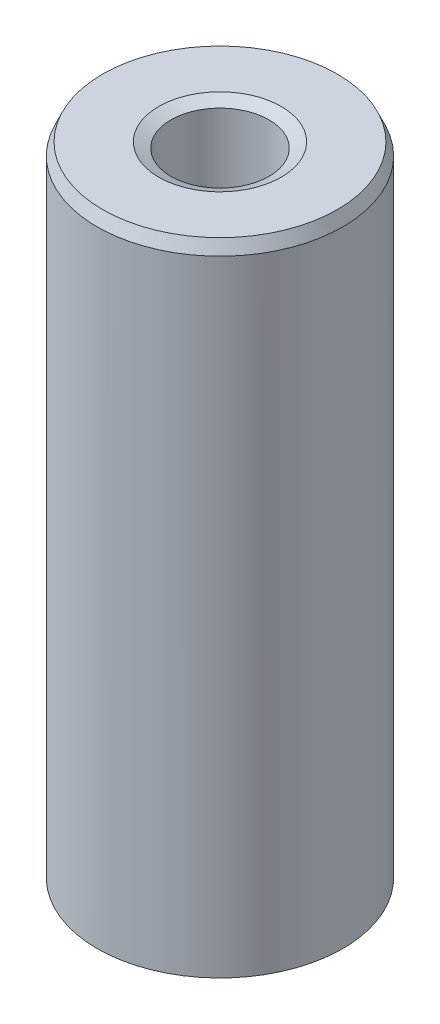
SolidWorks part; units mm, degrees
ref_plane "Front Plane" through (0, 0, 0) normal (0, 0, 1) x (1, 0, 0)
ref_plane "Top Plane" through (0, 0, 0) normal (0, 1, 0) x (1, 0, 0)
ref_plane "Right Plane" through (0, 0, 0) normal (1, 0, 0) x (0, 0, -1)
sketch "Sketch1" plane through (0, 0, 0) normal (0, 1, 0) x (1, 0, 0)
  circle A0 centre (0, 0) radius 7.5
  dimension "SLEEVE_OD" = 15
extrude "Boss-Extrude1" add sketch "Sketch1" along normal blind 39.2579
sketch "Sketch2" plane through (0, 0, 0) normal (0, 1, 0) x (1, 0, 0)
  circle A0 centre (0, 0) radius 2.9936
  dimension "BORE_D" = 5.9873
extrude "Cut-Extrude1" cut sketch "Sketch2" along normal through all
chamfer "Chamfer1" distance 0.7494 angle 23.887 4 edges at (0, 39.2579, 2.9936) (0, 0, 2.9936) (0, 0, 7.5) (0, 39.2579, 7.5) first distance on face at (0, 39.2579, 2.9936) first distance on face at (0, 0, 2.9936) first distance on face at (0, 39.2579, 7.5)
